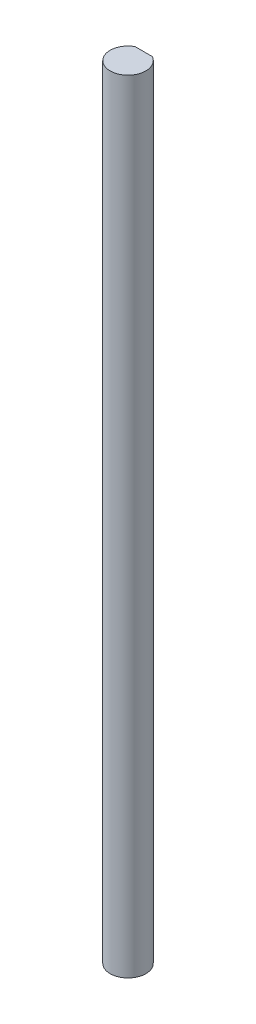
SolidWorks part; units mm, degrees
material "AISI 1045 Steel, cold drawn"
ref_plane "Front Plane" through (0, 0, 0) normal (0, 0, 1) x (1, 0, 0)
ref_plane "Top Plane" through (0, 0, 0) normal (0, 1, 0) x (1, 0, 0)
ref_plane "Right Plane" through (0, 0, 0) normal (1, 0, 0) x (0, 0, -1)
sketch "Sketch1" plane through (0, 0, 0) normal (0, 1, 0) x (1, 0, 0)
  line L0 (-1.9365, 3.5) -> (1.9365, 3.5)
  arc A0 (-1.9365, 3.5) -> (1.9365, 3.5) centre (0, 0) ccw
  dimension "D1" = 8
  dimension "D2" = 3.5
extrude "Boss-Extrude1" add sketch "Sketch1" along normal blind 175
